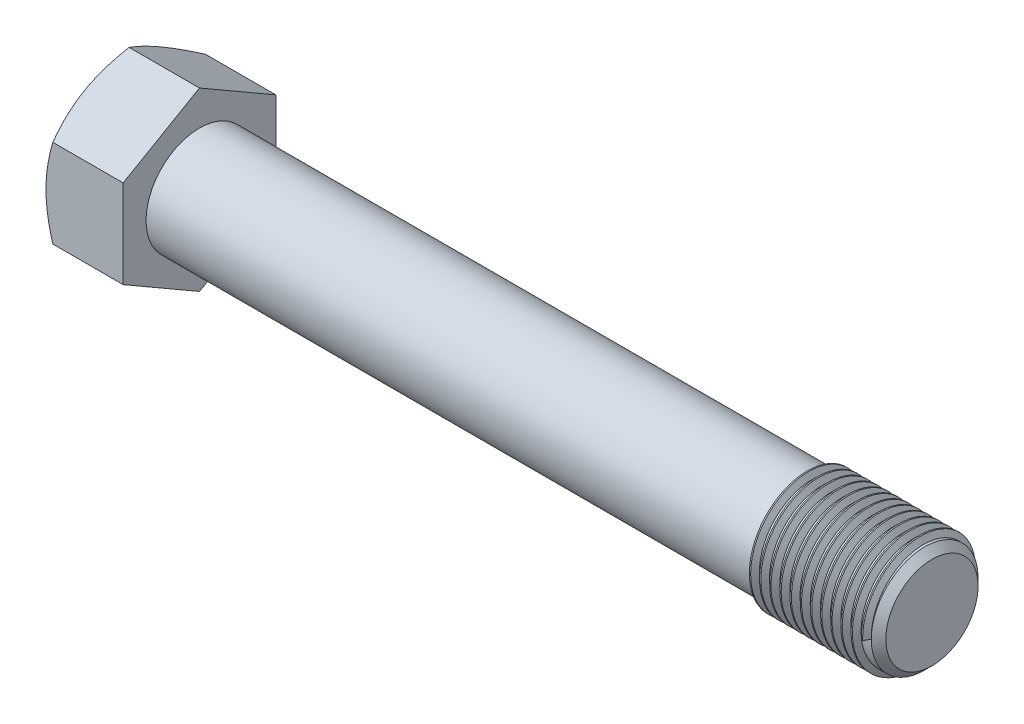
SolidWorks part; units mm, degrees
extrude "BaseHead" add sketch "Sketch1" along normal blind 8.0264
sketch "Sketch1" plane through (0, 0, 0) normal (1, 0, 0) x (0, 0, -1)
  line L0 (7.9375, 4.5827) -> (7.9375, -4.5827)
  line L1 (-7.9375, 4.5827) -> (-7.9375, -4.5827)
  line L2 (7.9375, -4.5827) -> (0, -9.1654)
  line L3 (0, -9.1654) -> (-7.9375, -4.5827)
  line L4 (7.9375, 4.5827) -> (0, 9.1654)
  line L5 (0, 9.1654) -> (-7.9375, 4.5827)
  dimension "D2" = 120
  dimension "D3" = 7.9375
  dimension "D4" = 7.9375
  dimension "D5" = 7.9375
ref_plane "Plane1" through (0, 0, 0) normal (0, 0, 1) x (1, 0, 0)
ref_plane "Plane2" through (0, 0, 0) normal (0, 1, 0) x (1, 0, 0)
ref_plane "Plane3" through (0, 0, 0) normal (1, 0, 0) x (0, 0, -1)
sketch "BodySke" plane through (0, 0, 0) normal (0, 0, 1) x (1, 0, 0)
  line L0 (0, 4.5827) -> (0, -4.5827) construction
  line L1 (0, 0) -> (84.2264, 0)
  line L2 (0, 0) -> (0, 5.5562)
  line L3 (0, 5.5562) -> (83.4708, 5.5562)
  line L4 (84.2264, 0) -> (84.2264, 4.8006)
  line L5 (8.0264, 9.1654) -> (8.0264, 4.5827) construction
  line L6 (84.2264, 4.8006) -> (83.4708, 5.5562)
  line L7 (0, 0) -> (96.52, 0) construction
  line L8 (84.2264, -4.8006) -> (83.4708, -5.5562) construction
  line L9 (0, -5.5562) -> (83.4708, -5.5562) construction
  line L10 (9.2964, 15.24) -> (9.2964, -2.54) construction
  line L11 (55.6514, 15.24) -> (55.6514, -2.54) construction
  line L12 (8.0264, 4.5827) -> (8.0264, -4.5827) construction
  dimension "Diameter" = 11.1125
revolve "BaseBody" add sketch "BodySke" angle 360 about L7
cosmetic thread "ThreadCosmetic" [suppressed] parameters "Thread_length"=28.575, "Thread_minor"=9.6012
sketch "Sketch3" plane through (0, 0, 0) normal (0, 0, 1) x (1, 0, 0)
  line L0 (0, 7.9375) -> (4.3751, 15.5154)
  line L1 (0, 9.1654) -> (0, 4.5827) construction
  line L2 (4.3751, 15.5154) -> (4.3751, 21.8654)
  line L3 (4.3751, 21.8654) -> (-12.7, 21.8654)
  line L4 (-12.7, 21.8654) -> (-12.7, 7.9375)
  line L5 (-12.7, 7.9375) -> (0, 7.9375)
  line L6 (0, 0) -> (99.06, 0) construction
  line L7 (8.0264, 9.1654) -> (0, 9.1654) construction
  dimension "D1" = 7.9375
  dimension "D2" = 6.35
  dimension "D3" = 12.7
  dimension "D4" = 6.35
  dimension "Head_ch_ang" = 30
revolve "HeadChamfer" cut sketch "Sketch3" angle 360 about L6
fillet "HeadFillet" [suppressed] radius 0.762
sketch "ThdSchSke" plane through (0, 0, 0) normal (0, 0, 1) x (1, 0, 0)
  line L0 (55.6514, -4.8006) -> (55.1223, -5.5563)
  line L1 (55.6514, -4.8006) -> (56.1805, -5.5562)
  line L2 (56.1805, -5.5562) -> (56.1805, -6.9453)
  line L3 (-3.175, 0) -> (5.1513, 0) construction
  line L5 (56.1805, -6.9453) -> (55.1223, -6.9453)
  line L6 (55.1223, -6.9453) -> (55.1223, -5.5563)
  dimension "Thread_minor" = 9.6012
  dimension "Diameter" = 11.1125
  dimension "Start" = 55.6514
revolve "ThreadSchematic" [suppressed] cut sketch "ThdSchSke" angle 360 about L3
pattern_linear "ThdSchPat" [suppressed]
thread "Thread1" pitch 1.0583 method extrude profile "Thread Profile1" start angle 0, offset 0, length 12.192, pitch 1.0583, diameter 11.1125
ref_plane "Plane4" through (83.4708, 0, 5.5562) normal (0, -1, 0) x (0, 0, 1)
sketch "Thread Profile1" plane through (83.4708, 0, 5.5562) normal (0, -1, 0) x (0, 0, 1)
  line L0 (0, 0) -> (0, 1.0583) construction
  line L1 (0, 0) -> (0.5728, 0.3307)
  line L2 (0.5728, 0.3307) -> (0.5728, 0.463)
  line L3 (0.5728, 0.463) -> (0, 0.7937)
  line L4 (0.5728, 0.3969) -> (0, 0.3969) construction
  line L11 (0, 0) -> (0, 0.7937)
  point P2 (0, 0)
  dimension "Pitch" = 1.0583
  dimension "Profile_Angle" = 60
  dimension "Profile_Land" = 0.1323
  dimension "Profile_Height" = 0.5728
equation "\"D3@Sketch1\" = \"Width_flats@Sketch1\" / 2"
equation "\"D4@Sketch1\" = \"D3@Sketch1\""
equation "\"D5@Sketch1\" = \"D4@Sketch1\""
equation "\"Thread_minor@ThreadCosmetic\" = \"Minor_dia@BodySke\""
equation "\"D1@Sketch3\" = \"Width_flats@Sketch1\" / 2"
equation "\"Thread_length@ThreadCosmetic\" = ((sgn( (\"Length@BodySke\" - \"Advance@BodySke\" ) - \"Thread_nom@BodySke\" )-1)*( (\"Length@BodySke\" - \"Advance@BodySke\" ) - \"Thread_nom@BodySke\" ))/-2+ \"Thread_nom@BodySke\""
equation "\"Thread_minor@ThdSchSke\" = \"Minor_dia@BodySke\""
equation "\"Diameter@ThdSchSke\" = \"Diameter@BodySke\""
equation "\"Overcut@ThdSchSke\" = \"Diameter@BodySke\" * 1.25"
equation "\"Start@ThdSchSke\" = \"Head_ht@BaseHead\" + \"Length@BodySke\" - \"Thread_length@ThreadCosmetic\"  '---Non-countersunk---"
equation "\"Num_threads@ThdSchPat\" = int( \"Thread_length@ThreadCosmetic\" / \"Advance@BodySke\" + 0.999 )  + 1"
equation "\"Advance@ThdSchPat\" = \"Thread_length@ThreadCosmetic\" /  (\"Num_threads@ThdSchPat\" - 1) 'relax it"
equation "\"Num_threads@ThdSchPat\" = \"Num_threads@ThdSchPat\" - sgn( \"Num_threads@ThdSchPat\" - 1) '---chamfered tips only---"
